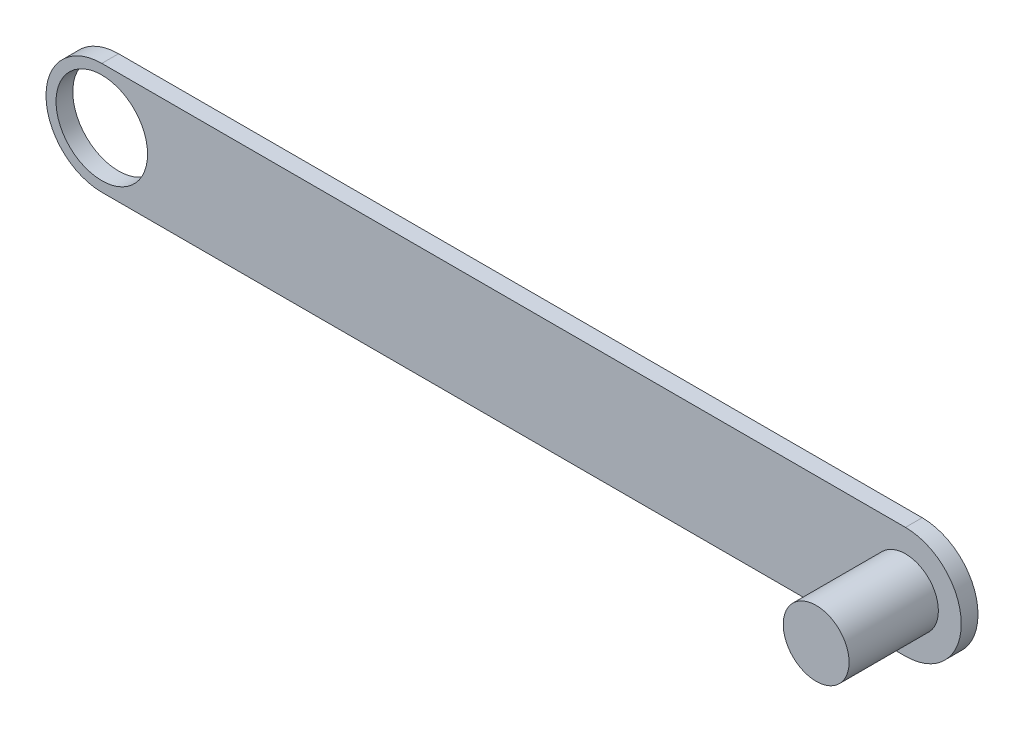
SolidWorks part; units mm, degrees
material "PBT General Purpose"
ref_plane "Front Plane" through (0, 0, 0) normal (0, 0, 1) x (1, 0, 0)
ref_plane "Top Plane" through (0, 0, 0) normal (0, 1, 0) x (1, 0, 0)
ref_plane "Right Plane" through (0, 0, 0) normal (1, 0, 0) x (0, 0, -1)
sketch "Sketch1" plane through (0, 0, 0) normal (0, 0, 1) x (1, 0, 0)
  line L0 (0, 5) -> (72, 5)
  line L6 (0, -5) -> (72, -5)
  arc A2 (0, 5) -> (0, -5) centre (0, 0) ccw
  arc A3 (72, -5) -> (72, 5) centre (72, 0) ccw
  dimension "D1" = 10
  dimension "D2" = 72
extrude "Boss-Extrude4" add sketch "Sketch1" along normal blind 1.5
sketch "Sketch4" plane through (0, 0, 1.5) normal (0, 0, 1) x (1, 0, 0)
  circle A0 centre (0, 0) radius 4.1
  dimension "D1" = 8.2
extrude "Cut-Extrude1" cut sketch "Sketch4" against normal through all
sketch "Sketch5" plane through (0, 0, 1.5) normal (0, 0, 1) x (1, 0, 0)
  circle A0 centre (72, 0) radius 2.95
  arc A3 (72, -5) -> (72, 5) centre (72, 0) ccw construction
  dimension "D1" = 5.9
extrude "Boss-Extrude5" add sketch "Sketch5" along normal blind 8
